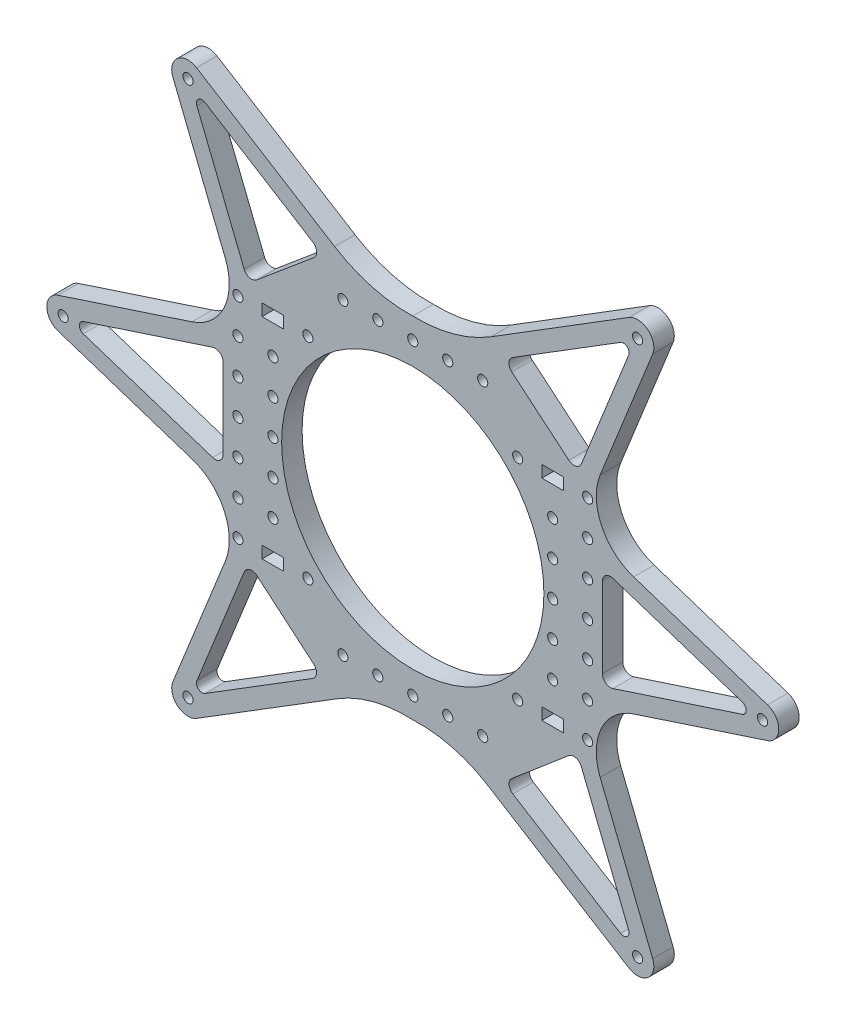
SolidWorks part; units mm, degrees
material "Acrylic (Medium-high impact)"
ref_plane "Front Plane" through (0, 0, 0) normal (0, 0, 1) x (1, 0, 0)
ref_plane "Top Plane" through (0, 0, 0) normal (0, 1, 0) x (1, 0, 0)
ref_plane "Right Plane" through (0, 0, 0) normal (1, 0, 0) x (0, 0, -1)
sketch "Sketch1" plane through (0, 0, 0) normal (0, 0, 1) x (1, 0, 0)
  line L0 (-447622.4345, 422.8828) -> (448935.6268, 422.8828) construction
  line L1 (587.9953, 497.7534) -> (603.0011, 460.347)
  line L2 (696.5962, 452.8828) -> (696.5962, 392.8828) construction
  line L3 (653.3971, 419.0702) -> (-31485.9834, -37883.1519) construction
  line L4 (699.6962, 394.5828) -> (693.4962, 391.1828) construction
  line L5 (699.6962, 391.1828) -> (693.4962, 394.5828) construction
  line L6 (594.8522, 494.09) -> (608.3693, 460.3949)
  line L7 (594.7755, 503.4426) -> (634.2359, 478.9202)
  line L8 (597.1925, 496.0537) -> (628.0285, 476.8909)
  line L9 (594.8522, 494.09) -> (597.1925, 496.0537) construction
  line L10 (699.6962, 391.1828) -> (693.4962, 391.1828)
  line L11 (693.4962, 394.5828) -> (693.4962, 391.1828)
  line L12 (699.6962, 394.5828) -> (693.4962, 394.5828)
  line L13 (594.7755, 503.4426) -> (587.9953, 497.7534) construction
  line L14 (628.2915, 473.1954) -> (611.963, 459.4942)
  line L15 (608.3693, 460.3949) -> (628.0285, 476.8909) construction
  line L16 (699.6962, 394.5828) -> (699.6962, 391.1828)
  line L17 (-343.4038, 422.8828) -> (49656.5962, 422.8828) construction
  line L18 (648.8948, 432.061) -> (-31490.4849, 38734.2822) construction
  line L19 (-347.3366, 472.8828) -> (49652.6634, 472.8828) construction
  line L20 (-347.2527, 372.8828) -> (49652.7473, 372.8828) construction
  line L21 (562.3601, 421.3552) -> (599.3601, 409.2322)
  line L22 (602.3601, 434.3594) -> (602.3601, 411.4062)
  line L23 (555.1462, 427.3082) -> (555.1462, 418.4573) construction
  line L24 (562.3601, 424.4103) -> (599.3601, 436.5334)
  line L25 (599.3601, 409.2322) -> (599.3601, 436.5334) construction
  line L26 (555.1462, 427.3082) -> (593.4467, 439.8574)
  line L27 (562.3601, 421.3552) -> (562.3601, 424.4103) construction
  line L28 (555.1462, 418.4573) -> (593.4521, 405.9064)
  line L29 (594.8981, 351.7823) -> (608.4028, 385.4215)
  line L30 (594.773, 342.323) -> (634.9941, 367.2934)
  line L31 (611.993, 386.3119) -> (628.262, 372.5303)
  line L32 (613.4962, 451.1828) -> (619.6962, 454.5828) construction
  line L33 (613.4962, 454.5828) -> (619.6962, 451.1828) construction
  line L34 (597.1926, 349.7103) -> (594.8981, 351.7823) construction
  line L35 (587.997, 348.0128) -> (594.773, 342.323) construction
  line L36 (627.9891, 368.8297) -> (608.4028, 385.4215) construction
  line L37 (597.1926, 349.7103) -> (627.9891, 368.8297)
  line L38 (587.997, 348.0128) -> (603.0086, 385.4056)
  line L39 (613.4962, 391.1828) -> (619.6962, 394.5828) construction
  line L40 (699.6962, 454.5828) -> (693.4962, 451.1828) construction
  line L41 (613.4962, 394.5828) -> (619.6962, 391.1828) construction
  line L42 (616.5962, 452.8828) -> (616.5962, 392.8828) construction
  line L43 (699.6962, 451.1828) -> (693.4962, 454.5828) construction
  line L44 (685.2033, 368.8297) -> (704.7896, 385.4215) construction
  line L45 (725.1954, 348.0128) -> (718.4193, 342.323) construction
  line L46 (715.9997, 349.7103) -> (718.2943, 351.7823) construction
  line L47 (750.8323, 421.3552) -> (750.8323, 424.4103) construction
  line L48 (713.8323, 409.2322) -> (713.8323, 436.5334) construction
  line L49 (758.0462, 427.3082) -> (758.0462, 418.4573) construction
  line L50 (704.8231, 460.3949) -> (685.1639, 476.8909) construction
  line L51 (718.4169, 503.4426) -> (725.1971, 497.7534) construction
  line L52 (718.3402, 494.09) -> (715.9998, 496.0537) construction
  line L53 (613.4962, 454.5828) -> (619.6962, 454.5828)
  line L54 (619.6962, 451.1828) -> (619.6962, 454.5828)
  line L55 (613.4962, 451.1828) -> (619.6962, 451.1828)
  line L56 (699.6962, 451.1828) -> (699.6962, 454.5828)
  line L57 (699.6962, 451.1828) -> (693.4962, 451.1828)
  line L58 (693.4962, 451.1828) -> (693.4962, 454.5828)
  line L59 (699.6962, 454.5828) -> (693.4962, 454.5828)
  line L60 (725.1954, 348.0128) -> (710.1838, 385.4056)
  line L61 (715.9997, 349.7103) -> (685.2033, 368.8297)
  line L62 (701.1994, 386.3119) -> (684.9304, 372.5303)
  line L63 (718.4193, 342.323) -> (678.1983, 367.2934)
  line L64 (718.2943, 351.7823) -> (704.7896, 385.4215)
  line L65 (758.0462, 418.4573) -> (719.7403, 405.9064)
  line L66 (758.0462, 427.3082) -> (719.7457, 439.8574)
  line L67 (750.8323, 424.4103) -> (713.8323, 436.5334)
  line L68 (710.8323, 434.3594) -> (710.8323, 411.4062)
  line L69 (750.8323, 421.3552) -> (713.8323, 409.2322)
  line L70 (613.4962, 451.1828) -> (613.4962, 454.5828)
  line L71 (684.9009, 473.1954) -> (701.2294, 459.4942)
  line L72 (613.4962, 394.5828) -> (613.4962, 391.1828)
  line L73 (613.4962, 394.5828) -> (619.6962, 394.5828)
  line L74 (619.6962, 394.5828) -> (619.6962, 391.1828)
  line L75 (715.9998, 496.0537) -> (685.1639, 476.8909)
  line L76 (718.4169, 503.4426) -> (678.9565, 478.9202)
  line L77 (718.3402, 494.09) -> (704.8231, 460.3949)
  line L78 (725.1971, 497.7534) -> (710.1912, 460.347)
  line L79 (613.4962, 391.1828) -> (619.6962, 391.1828)
  line L80 (706.5962, 432.8828) -> (696.5962, 432.8828) construction
  line L81 (706.5962, 422.8828) -> (706.5962, 432.8828) construction
  line L111 (656.5962, -513.6368) -> (656.5962, 49486.3632) construction
  arc A0 (597.1925, 496.0537) -> (594.8522, 494.09) centre (596.3441, 494.6884) ccw
  arc A1 (587.9953, 497.7534) -> (594.7755, 503.4426) centre (592.3174, 499.4872) cw
  circle A2 centre (592.3174, 499.4872) radius 1.45
  arc A4 (608.3693, 460.3949) -> (611.963, 459.4942) centre (610.4925, 461.2467) ccw
  arc A5 (628.2915, 473.1954) -> (628.0285, 476.8909) centre (626.821, 474.9479) ccw
  circle A6 centre (592.3174, 499.4872) radius 4.6569 construction
  circle A7 centre (706.5962, 432.8828) radius 1.45
  circle A8 centre (706.5962, 442.8828) radius 1.45
  circle A9 centre (706.5962, 452.8828) radius 1.45
  circle A10 centre (706.5962, 392.8828) radius 1.45
  arc A11 (555.1462, 418.4573) -> (555.1462, 427.3082) centre (556.5962, 422.8828) cw
  circle A12 centre (556.5962, 422.8828) radius 1.45
  circle A13 centre (646.5962, 378.8828) radius 1.45
  circle A14 centre (556.5962, 422.8828) radius 4.6569 construction
  arc A15 (562.3601, 424.4103) -> (562.3601, 421.3552) centre (562.8606, 422.8828) ccw
  circle A16 centre (656.5962, 422.8828) radius 37.5
  circle A18 centre (636.5962, 378.8828) radius 1.45
  arc A19 (602.3601, 434.3594) -> (599.3601, 436.5334) centre (600.0724, 434.3594) ccw
  circle A20 centre (706.5962, 402.8828) radius 1.45
  arc A21 (599.3601, 409.2322) -> (602.3601, 411.4062) centre (600.0724, 411.4062) ccw
  circle A22 centre (656.5962, 466.8828) radius 1.45
  circle A23 centre (696.5962, 432.8828) radius 1.45
  circle A24 centre (592.3174, 346.2783) radius 4.6556 construction
  arc A25 (627.9891, 368.8297) -> (628.262, 372.5303) centre (626.7787, 370.7793) ccw
  arc A27 (594.773, 342.323) -> (587.997, 348.0128) centre (592.3174, 346.2783) cw
  arc A28 (594.8981, 351.7823) -> (597.1926, 349.7103) centre (596.3441, 351.0771) ccw
  arc A29 (611.993, 386.3119) -> (608.4028, 385.4215) centre (610.519, 384.5719) ccw
  circle A31 centre (592.3174, 346.2783) radius 1.45
  circle A32 centre (706.5962, 412.8828) radius 1.45
  arc A33 (593.4521, 405.9064) -> (603.0086, 385.4056) centre (588.6268, 391.1793) cw
  circle A34 centre (656.5962, 378.8828) radius 1.45
  arc A35 (593.4467, 439.8574) -> (603.0011, 460.347) centre (588.6231, 454.5791) ccw
  circle A37 centre (696.5962, 442.8828) radius 1.45
  circle A38 centre (696.5962, 402.8828) radius 1.45
  arc A39 (634.9941, 367.2934) -> (656.5962, 372.8828) centre (654.7533, 335.4663) cw
  arc A40 (634.2359, 478.9202) -> (656.5962, 472.8828) centre (655.447, 513.0523) ccw
  circle A41 centre (720.8749, 346.2783) radius 4.6556 construction
  circle A42 centre (756.5962, 422.8828) radius 4.6569 construction
  circle A43 centre (696.5962, 412.8828) radius 1.45
  circle A44 centre (646.5962, 466.8828) radius 1.45
  circle A45 centre (636.5962, 466.8828) radius 1.45
  circle A46 centre (720.8749, 499.4872) radius 4.6569 construction
  circle A47 centre (696.5962, 422.8828) radius 1.45
  circle A48 centre (676.5962, 466.8828) radius 1.45
  circle A49 centre (666.5962, 466.8828) radius 1.45
  circle A50 centre (706.5962, 422.8828) radius 1.45
  arc A51 (678.9565, 478.9202) -> (656.5962, 472.8828) centre (657.7454, 513.0523) cw
  arc A52 (678.1983, 367.2934) -> (656.5962, 372.8828) centre (658.4391, 335.4663) ccw
  circle A53 centre (686.5962, 452.8828) radius 1.45
  circle A54 centre (686.5962, 392.8828) radius 1.45
  arc A55 (719.7457, 439.8574) -> (710.1912, 460.347) centre (724.5693, 454.5791) cw
  arc A56 (719.7403, 405.9064) -> (710.1838, 385.4056) centre (724.5656, 391.1793) ccw
  circle A57 centre (626.5962, 392.8828) radius 1.45
  circle A58 centre (720.8749, 346.2783) radius 1.45
  arc A59 (701.1994, 386.3119) -> (704.7896, 385.4215) centre (702.6733, 384.5719) cw
  arc A60 (718.2943, 351.7823) -> (715.9997, 349.7103) centre (716.8483, 351.0771) cw
  arc A61 (718.4193, 342.323) -> (725.1954, 348.0128) centre (720.8749, 346.2783) ccw
  arc A62 (685.2033, 368.8297) -> (684.9304, 372.5303) centre (686.4136, 370.7793) cw
  arc A63 (713.8323, 409.2322) -> (710.8323, 411.4062) centre (713.12, 411.4062) cw
  arc A64 (710.8323, 434.3594) -> (713.8323, 436.5334) centre (713.12, 434.3594) cw
  circle A65 centre (676.5962, 378.8828) radius 1.45
  arc A66 (750.8323, 424.4103) -> (750.8323, 421.3552) centre (750.3318, 422.8828) cw
  circle A67 centre (666.5962, 378.8828) radius 1.45
  circle A68 centre (756.5962, 422.8828) radius 1.45
  arc A69 (758.0462, 418.4573) -> (758.0462, 427.3082) centre (756.5962, 422.8828) ccw
  circle A70 centre (626.5962, 452.8828) radius 1.45
  circle A71 centre (606.5962, 422.8828) radius 1.45
  circle A72 centre (616.5962, 422.8828) radius 1.45
  circle A73 centre (616.5962, 412.8828) radius 1.45
  arc A74 (684.9009, 473.1954) -> (685.1639, 476.8909) centre (686.3714, 474.9479) cw
  arc A75 (704.8231, 460.3949) -> (701.2294, 459.4942) centre (702.6999, 461.2467) cw
  circle A76 centre (720.8749, 499.4872) radius 1.45
  arc A77 (725.1971, 497.7534) -> (718.4169, 503.4426) centre (720.8749, 499.4872) ccw
  arc A78 (715.9998, 496.0537) -> (718.3402, 494.09) centre (716.8483, 494.6884) cw
  circle A79 centre (616.5962, 402.8828) radius 1.45
  circle A80 centre (616.5962, 442.8828) radius 1.45
  circle A81 centre (606.5962, 412.8828) radius 1.45
  circle A82 centre (616.5962, 432.8828) radius 1.45
  circle A83 centre (606.5962, 402.8828) radius 1.45
  circle A84 centre (606.5962, 392.8828) radius 1.45
  circle A85 centre (606.5962, 452.8828) radius 1.45
  circle A86 centre (606.5962, 442.8828) radius 1.45
  circle A87 centre (606.5962, 432.8828) radius 1.45
  circle A279 centre (626.5962, 466.8828) radius 1.45 [skipped]
  circle A282 centre (626.5962, 378.8828) radius 1.45 [skipped]
  point P2 (620.1272, 466.3448)
  point P4 (604.6798, 472.924)
  point P5 (610.6788, 407.5004)
  point P6 (604.4937, 430.5743)
  point P7 (590.1096, 382.987)
  point P9 (656.5962, 422.8828)
  point P10 (592.2236, 451.9603)
  point P12 (560.2236, 451.9603)
  point P13 (615.5787, 412.0526)
  point P15 (596.4648, 452.5325)
  point P16 (593.7956, 519.1439)
  point P18 (562.0153, 451.7438)
  point P19 (589.0273, 503.4082)
  point P21 (557.1601, 445.912)
  point P22 (691.7574, 496.0365)
  point P23 (586.2073, 519.1355)
  point P25 (696.5962, 452.8828)
  point P27 (593.4054, 384.161)
  point P31 (706.9167, 384.1702)
  point P32 (709.3005, 386.1481)
  point P33 (712.3266, 520.5499)
  point P34 (710.2125, 451.5766)
  point P37 (593.7956, 519.1439)
  point P38 (704.5328, 382.1922)
  point P40 (675.1867, 401.4708)
  point P41 (685.2778, 409.8289)
  point P43 (705.5495, 376.706)
  point P44 (637.2651, 404.097)
  point P46 (743.1543, 445.9191)
  point P47 (656.5962, 422.8828)
  point P48 (685.1467, 493.2598)
  point P49 (742.2125, 451.5766)
  point P53 (695.1768, 484.8286)
  point P55 (708.8884, 517.1528)
  point P56 (706.5155, 519.1439)
  point P57 (714.1038, 519.1355)
  point P64 (708.6406, 384.393)
  point P66 (665.171, 499.4399)
  point P67 (704.1427, 521.135)
  point P80 (602.3601, 422.8828)
  point P86 (499.5503, 435.3778)
  point P106 (620.1275, 379.4211)
  point P114 (563.3616, 328.8714)
  point P127 (696.5962, 422.8828)
  point P143 (704.687, 438.4721)
  point P145 (738.2906, 448.6533)
  point P146 (704.7346, 451.575)
  point P147 (738.2991, 451.7509)
  point P148 (738.3077, 454.8484)
  point P241 (656.5962, 389.3729)
  point P244 (749.8308, 328.8714)
  point P245 (693.0649, 379.4211)
  point P246 (710.8323, 422.8828)
  point P247 (696.5962, 422.8828)
  point P248 (724.165, 503.4082)
  point P249 (693.0651, 466.3448)
  dimension "D2" = 2.9
  dimension "D3" = 6.2644
  dimension "D6" = 4
  dimension "D9" = 4
  dimension "D7" = 4
  dimension "D11" = 100
  dimension "D12" = 5
  dimension "D5" = 5
  dimension "D19" = 50
  dimension "D20" = 100
  dimension "D25" = 6.2644
  dimension "D13" = 3
  dimension "D15" = 37
  dimension "D18" = 40
  dimension "D39" = 3.4
  dimension "D37" = 2.9
  dimension "D38" = 75
  dimension "D8" = 50
  dimension "D10" = 30
  dimension "D14" = 50
  dimension "D16" = 37
  dimension "D17" = 2
  dimension "D21" = 44
  dimension "D24" = 5
  dimension "D26" = 3
  dimension "D27" = 10
  dimension "D29" = 5
  dimension "D30" = 6.2644
  dimension "D31" = 3
  dimension "D32" = 37
  dimension "D33" = 10
  dimension "D34" = 100
  dimension "D35" = 5
  dimension "D36" = 5
  dimension "D41" = 6.2
extrude "Boss-Extrude1" add sketch "Sketch1" along normal blind 5.85
